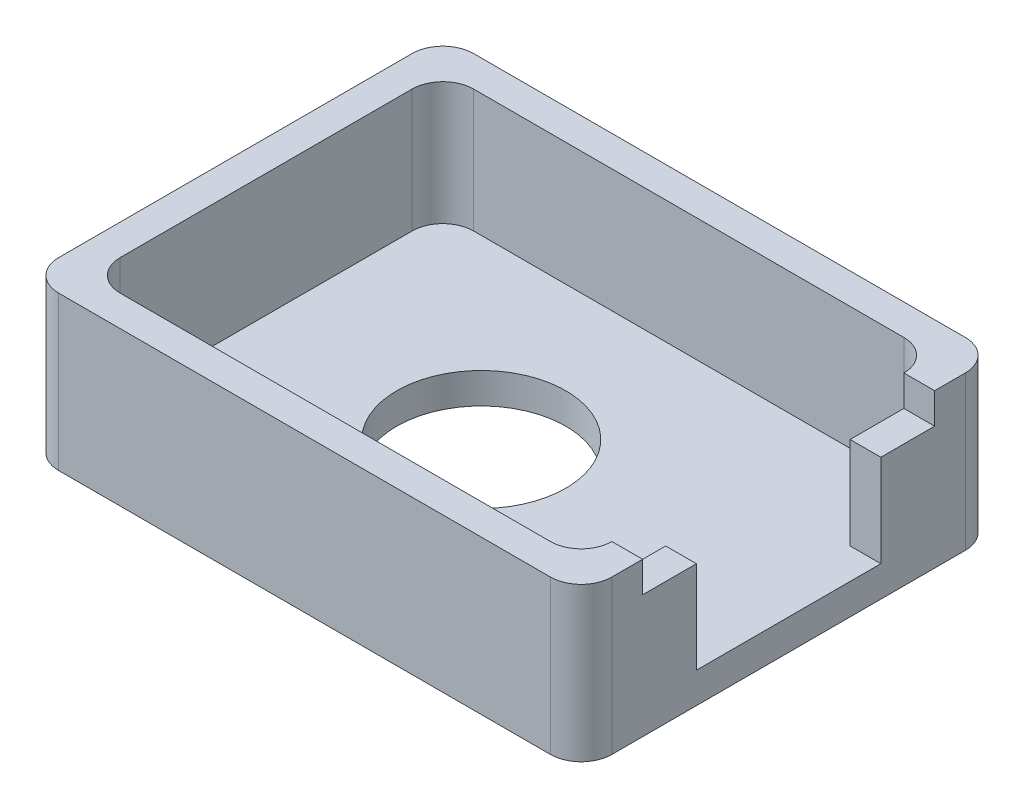
SolidWorks part; units mm, degrees
ref_plane "Front Plane" through (0, 0, 0) normal (0, 0, 1) x (1, 0, 0)
ref_plane "Top Plane" through (0, 0, 0) normal (0, 1, 0) x (1, 0, 0)
ref_plane "Right Plane" through (0, 0, 0) normal (1, 0, 0) x (0, 0, -1)
sketch "Sketch1" plane through (0, 0, 0) normal (0, 1, 0) x (1, 0, 0)
  line L0 (-18, 0) -> (18, 0) construction
  line L1 (-18, -13.5) -> (18, -13.5)
  line L2 (-18, -13.5) -> (-18, 13.5)
  line L3 (-18, 13.5) -> (18, 13.5)
  line L4 (18, -13.5) -> (18, 13.5)
  line L5 (-18, -13.5) -> (18, 13.5) construction
  line L6 (-18, 13.5) -> (18, -13.5) construction
  circle A0 centre (-2, 0) radius 5.5
  point P0 (0, 0)
  dimension "D3" = 11
  dimension "D1" = 36
  dimension "D2" = 27
  dimension "D4" = 16
extrude "Boss-Extrude1" add sketch "Sketch1" along normal blind 2
sketch "Sketch2" plane through (0, 2, 0) normal (0, 1, 0) x (1, 0, 0)
  line L0 (18, 13.5) -> (-18, 13.5)
  line L1 (-18, 13.5) -> (-18, -13.5)
  line L2 (-18, -13.5) -> (18, -13.5)
  line L3 (18, -13.5) -> (18, -9.5)
  line L4 (18, -13.5) -> (18, 13.5) construction
  line L5 (18, -9.5) -> (16, -9.5)
  line L6 (16, -9.5) -> (16, -11.5)
  line L7 (16, -11.5) -> (-16, -11.5)
  line L8 (-16, -11.5) -> (-16, 11.5)
  line L9 (-16, 11.5) -> (16, 11.5)
  line L10 (16, 11.5) -> (16, 9.5)
  line L11 (16, 9.5) -> (18, 9.5)
  line L12 (18, 9.5) -> (18, 13.5)
  dimension "D1" = 2
  dimension "D2" = 2
  dimension "D3" = 2
  dimension "D4" = 2
  dimension "D5" = 2
  dimension "D6" = 2
  dimension "D7" = 2
extrude "Boss-Extrude2" add sketch "Sketch2" along normal blind 8
sketch "Sketch3" plane through (18, 0, 0) normal (1, 0, 0) x (0, 0, -1)
  line L0 (0, 0) -> (0, 10) construction
  line L1 (-11.5, 10) -> (11.5, 10) construction
  line L2 (-9.5, 8) -> (-6, 8)
  line L4 (-9.5, 10) -> (-9.5, 2) construction
  line L5 (-6, 8) -> (-6, 2)
  line L9 (-9.5, 8) -> (-9.5, 2)
  line L10 (-9.5, 2) -> (-6, 2)
  line L11 (9.5, 8) -> (9.5, 2)
  line L12 (9.5, 8) -> (6, 8)
  line L13 (6, 8) -> (6, 2)
  line L14 (9.5, 2) -> (6, 2)
  dimension "D1" = 6
  dimension "D2" = 2
  dimension "D3" = 8
extrude "Boss-Extrude3" add sketch "Sketch3" against normal up to surface (2 mm away) up to face at (16, 6, 10.5)
fillet "Fillet2" radius 2 8 edges at (-18, 5, 13.5) (-18, 5, -13.5) (18, 5, -13.5) (18, 5, 13.5) (16, 6, -11.5) (16, 6, 11.5) (-16, 6, 11.5) (-16, 6, -11.5)
